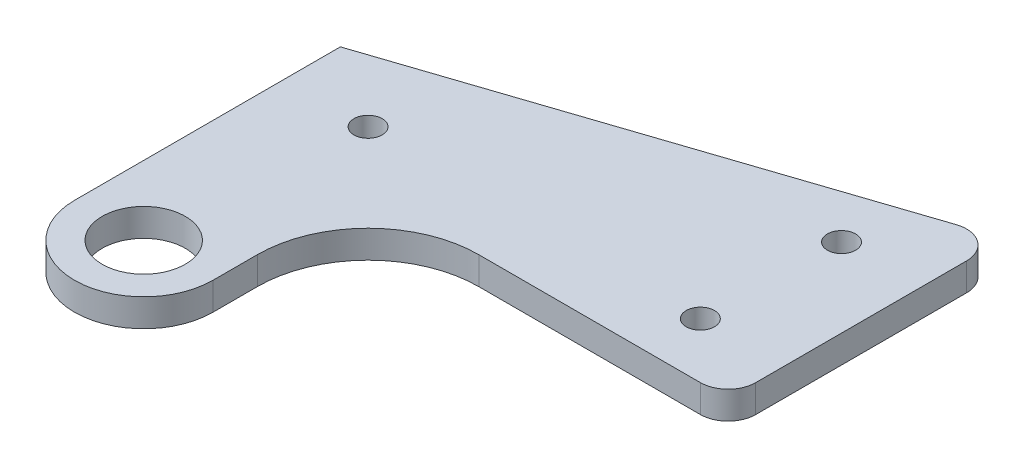
SolidWorks part; units mm, degrees
ref_plane "正面" through (0, 0, 0) normal (0, 0, 1) x (1, 0, 0)
ref_plane "平面" through (0, 0, 0) normal (0, 1, 0) x (1, 0, 0)
ref_plane "右側面" through (0, 0, 0) normal (1, 0, 0) x (0, 0, -1)
sketch "ｽｹｯﾁ1" plane through (0, 0, 0) normal (0, 1, 0) x (1, 0, 0)
  line L0 (0, 0) -> (180, 0) construction
  line L1 (180, 0) -> (180, 60) construction
  line L2 (0, 0) -> (0, -48)
  line L3 (0, -48) -> (25, -48) construction
  line L4 (25, -48) -> (25, -20)
  line L5 (180, 60) -> (0, 0) construction
  line L6 (0, 0) -> (90, 30)
  line L7 (90, 30) -> (90, -20)
  line L8 (90, -20) -> (25, -20)
  line L9 (0, -10) -> (90, -10) construction
  line L10 (90, 19.4591) -> (0, -10.5409) construction
  arc A0 (0, -48) -> (25, -48) centre (12.5, -48) ccw
  circle A1 centre (75.7698, 14.7157) radius 2.55
  circle A2 centre (75, -10) radius 2.55
  circle A3 centre (15, -10) radius 2.55
  circle A4 centre (12.5, -48) radius 7.5
  dimension "D5" = 25
  dimension "D9" = 15
  dimension "D12" = 5.1
  dimension "D13" = 15
  dimension "D1" = 60
  dimension "D2" = 180
  dimension "D3" = 20
  dimension "D4" = 90
  dimension "D6" = 28
  dimension "D7" = 10
  dimension "D8" = 10
  dimension "D10" = 15
  dimension "D11" = 15
extrude "ﾎﾞｽ - 押し出し1" add sketch "ｽｹｯﾁ1" along normal blind 5
fillet "ﾌｨﾚｯﾄ1" radius 20 1 edges at (25, 2.5, 20)
fillet "ﾌｨﾚｯﾄ2" radius 5 2 edges at (90, 2.5, -30) (90, 2.5, 20)
